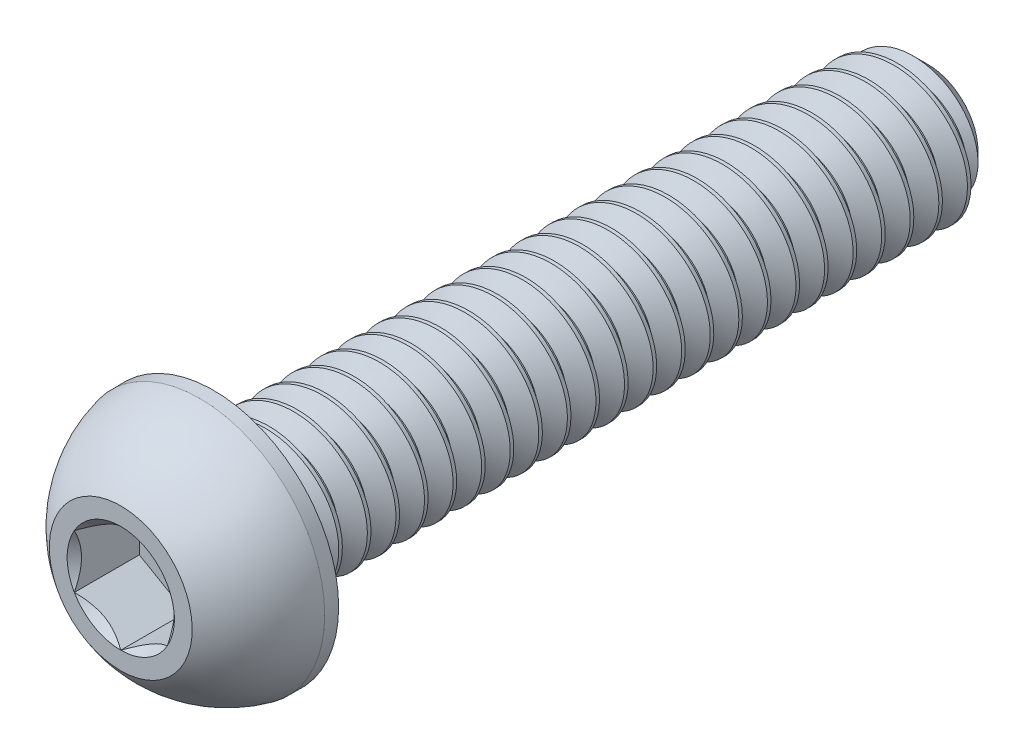
SolidWorks part; units mm, degrees
ref_plane "Front" through (0, 0, 0) normal (0, 0, 1) x (1, 0, 0)
ref_plane "Top" through (0, 0, 0) normal (0, 1, 0) x (1, 0, 0)
ref_plane "Right" through (0, 0, 0) normal (1, 0, 0) x (0, 0, -1)
sketch "Sketch1" plane through (0, 0, 0) normal (1, 0, 0) x (0, 0, -1)
  line L2 (1.3, 1) -> (11.3, 1)
  line L3 (11.3, 1) -> (11.3, 0)
  line L4 (11.3, 0) -> (1.3, 0)
  line L6 (1.105, 1.75) -> (1.3, 1.75) construction
  line L7 (11.3, 1) -> (11.3, -1) construction
  line L8 (0, 0) -> (1.3, 0) construction
  line L9 (1.3, 1.75) -> (1.3, -1.75) construction
  line L11 (1.3, 1) -> (1.3, 0)
  line L13 (0, 0.65) -> (0, -0.65) construction
  line L14 (0, 0.65) -> (0, 1) construction
  arc A3 (0, 1) -> (1.105, 1.75) centre (1.4858, 0) cw construction
  dimension "D1" = 0.195
revolve "Revolve1" add sketch "Sketch1" angle 360 mid plane about L4
sketch "Sketch3" plane through (0, 0, -11.3) normal (0, 0, -1) x (-1, 0, 0)
  circle A0 centre (0, 0) radius 1
curve "Helix/Spiral1" pitch 0.4 height 10.4 radius 1 centre (0, 0, -11.3) axis (0, 0, 1) start towards (1, 0, 0)
sketch "Sketch2" plane through (0, 0, 0) normal (1, 0, 0) x (0, 0, -1)
  line L0 (11.2, 1) -> (11.55, 1) construction
  line L1 (11.55, 1) -> (11.375, 0.6969) construction
  line L2 (11.375, 0.6969) -> (11.2, 1) construction
  line L3 (11.275, 0.8701) -> (11.475, 0.8701) construction
  line L4 (11.35, 0.7402) -> (11.4, 0.7402) construction
  line L5 (11.375, 0.7402) -> (11.375, 1) construction
  line L6 (11.2, 1) -> (11.55, 1)
  line L7 (11.55, 1) -> (11.4, 0.7402)
  line L8 (11.4, 0.7402) -> (11.35, 0.7402)
  line L9 (11.35, 0.7402) -> (11.2, 1)
  point P9 (11.375, 0.8701)
  dimension "D1" = 0.2
  dimension "D2" = 0.05
chamfer "Chamfer1" distance 0.3 angle 45 1 edges at (0, 1, -11.3)
sweep "Cut-Sweep1" cut profiles "Sketch2" path "Helix/Spiral1" align with end faces yes
sketch "Sketch7" plane through (0, 0, 0) normal (1, 0, 0) x (0, 0, -1)
  line L6 (1.105, 1.75) -> (1.3, 1.75) construction
  line L8 (0, 0) -> (1.3, 0) construction
  line L11 (1.3, 1.75) -> (1.3, -1.75) construction
  line L12 (1.105, 1.75) -> (1.3, 1.75)
  line L13 (0, 0) -> (1.3, 0)
  line L14 (0, 0.65) -> (0, -0.65) construction
  line L15 (1.3, 1.75) -> (1.3, 0)
  line L16 (0, 1) -> (0, 0)
  arc A2 (1.105, 1.75) -> (0, 1) centre (1.4858, 0) ccw construction
  arc A3 (1.105, 1.75) -> (0, 1) centre (1.4858, 0) ccw
revolve "Revolve2" add sketch "Sketch7" angle 360 mid plane about L13
sketch "Sketch5" plane through (0, 0, 0) normal (0, 0, 1) x (1, 0, 0)
  line L1 (0.65, -0.3753) -> (0.65, 0.3753)
  line L2 (0.65, 0.3753) -> (0, 0.7506)
  line L3 (0, 0.7506) -> (-0.65, 0.3753)
  line L4 (-0.65, 0.3753) -> (-0.65, -0.3753)
  line L5 (-0.65, -0.3753) -> (0, -0.7506)
  line L6 (0, -0.7506) -> (0.65, -0.3753)
  circle A0 centre (0, 0) radius 0.65 construction
extrude "Cut-Extrude2" cut sketch "Sketch5" against normal blind 0.91
sketch "Sketch6" plane through (0, 0, 0) normal (0, 0, 1) x (1, 0, 0)
  circle A0 centre (0, 0) radius 0.7506
extrude "Cut-Extrude3" cut sketch "Sketch6" against normal blind 0.91 draft 45
sketch "Sketch9" [suppressed] plane through (0, 0, -5.0546) normal (0, 0, 1) x (1, 0, 0)
  circle A2 centre (0, 0) radius 4.7625
extrude "Boss-Extrude2" [suppressed] add sketch "Sketch9" against normal offset from surface (6.35 mm away) 31.75 up to face at (0, 0.7, -11.3)
sketch "Sketch10" plane through (0, 0, 0) normal (1, 0, 0) x (0, 0, -1)
  line L0 (11.3, 1) -> (11.3, -1) construction
  point P0 (10.7, -1)
  dimension "D1" = 0.6
equation "\"D3@Helix/Spiral1\"=\"Lg@Sketch1\" + (\"D4@Helix/Spiral1\")"
equation "\"D1@Chamfer1\" = \"D4@Helix/Spiral1\" * .75"
equation "\"D1@Cut-Extrude2\" = \"Head Ht@Sketch1\" * .7"
equation "\"D1@Sketch1\" = \"Head Ht@Sketch1\" * .15"
equation "\"D1@Sketch10\" = \"D4@Helix/Spiral1\" * 1.5"
equation "\"D1@Cut-Extrude3\" = \"D1@Cut-Extrude2\""
equation "\"D1@Sketch2\"=\"D4@Helix/Spiral1\"*.5"
equation "\"D2@Sketch2\"=\"D4@Helix/Spiral1\"*.125"
